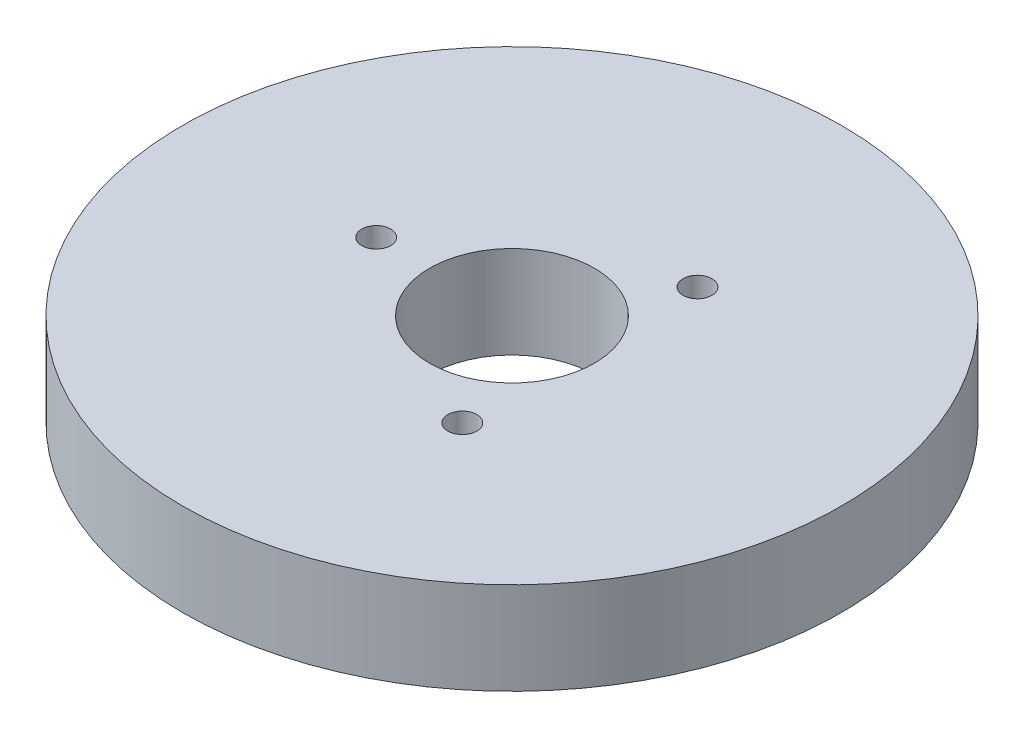
SolidWorks part; units mm, degrees
ref_plane "Front Plane" through (0, 0, 0) normal (0, 0, 1) x (1, 0, 0)
ref_plane "Top Plane" through (0, 0, 0) normal (0, 1, 0) x (1, 0, 0)
ref_plane "Right Plane" through (0, 0, 0) normal (1, 0, 0) x (0, 0, -1)
sketch "Sketch1" plane through (0, 0, 0) normal (0, 1, 0) x (1, 0, 0)
  circle A0 centre (0, 0) radius 100
  dimension "FLANGE_OD" = 200
extrude "Boss-Extrude1" add sketch "Sketch1" along normal blind 28
sketch "Sketch2" plane through (0, 0, 0) normal (0, 1, 0) x (1, 0, 0)
  circle A0 centre (0, 0) radius 25
  dimension "BORE_D" = 50
extrude "Cut-Extrude1" cut sketch "Sketch2" along normal through all
sketch "Sketch3" plane through (0, 28, 0) normal (0, 1, 0) x (1, 0, 0)
  circle A0 centre (0, 0) radius 41.2017 construction
  circle A1 centre (-41.2017, 0) radius 4.3866
  dimension "BOLT_D" = 8.7732
  dimension "BOLT_PCD" = 82.4034
extrude "Cut-Extrude2" cut sketch "Sketch3" against normal blind 23.8377
pattern_circular "CirPattern1" count 3 over 360 about axis through (0, 0, 0) along (0, 1, 0) of "Cut-Extrude2"
